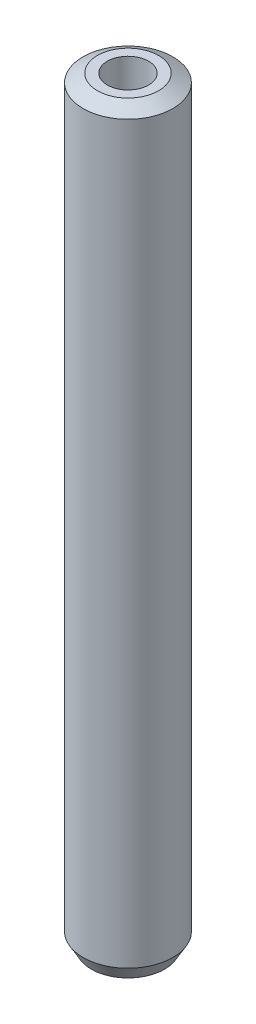
SolidWorks part; units mm, degrees
ref_plane "Front Plane" through (0, 0, 0) normal (0, 0, 1) x (1, 0, 0)
ref_plane "Top Plane" through (0, 0, 0) normal (0, 1, 0) x (1, 0, 0)
ref_plane "Right Plane" through (0, 0, 0) normal (1, 0, 0) x (0, 0, -1)
sketch "Sketch1" plane through (0, 0, 0) normal (0, 1, 0) x (1, 0, 0)
  circle A0 centre (0, 0) radius 25
  dimension "SHAFT_OD" = 50
extrude "Boss-Extrude1" add sketch "Sketch1" along normal blind 422.0615
sketch "Sketch2" plane through (0, 0, 0) normal (0, 1, 0) x (1, 0, 0)
  circle A0 centre (0, 0) radius 11.5133
  dimension "BORE_D" = 23.0265
extrude "Cut-Extrude1" cut sketch "Sketch2" along normal through all
chamfer "Chamfer1" distance 4.5988 angle 60 2 edges at (0, 422.0615, 25) (0, 0, 25) first distance on face at (0, 422.0615, 25) first distance on face at (0, 0, 11.5133)
